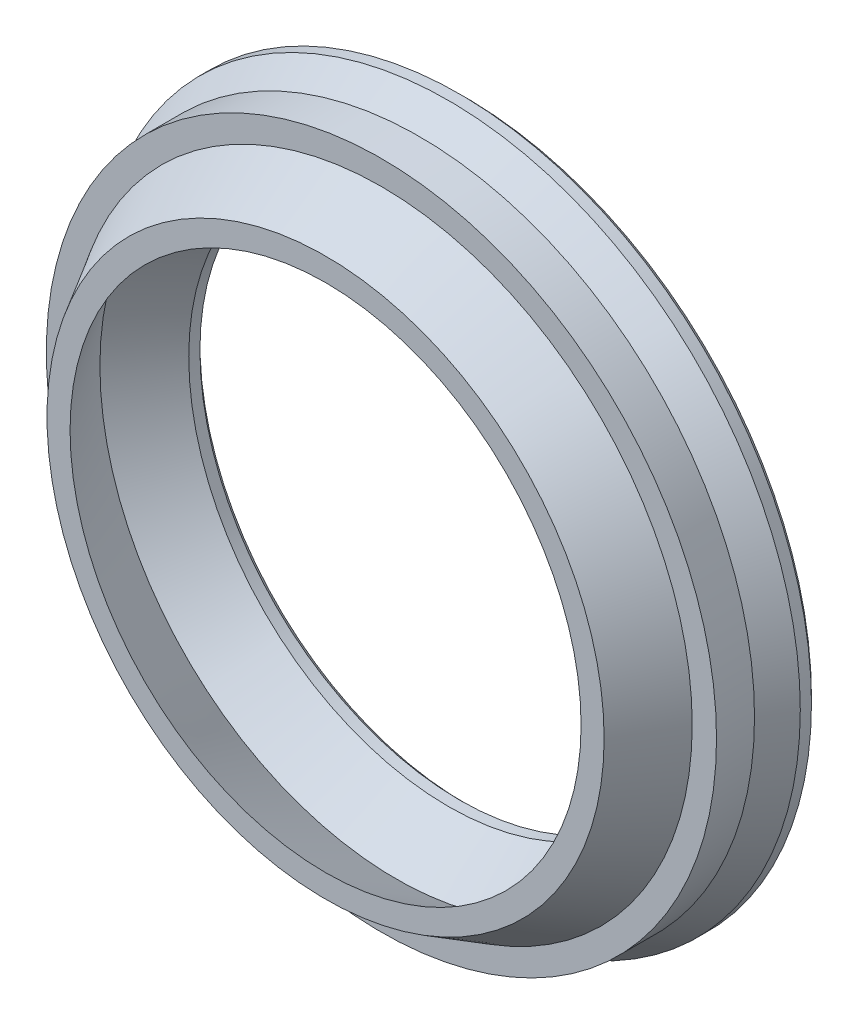
SolidWorks part; units mm, degrees
ref_plane "Front" through (0, 0, 0) normal (0, 0, 1) x (1, 0, 0)
ref_plane "Top" through (0, 0, 0) normal (0, 1, 0) x (1, 0, 0)
ref_plane "Right" through (0, 0, 0) normal (1, 0, 0) x (0, 0, -1)
sketch "Sketch1" plane through (21, 0, -3.1487) normal (0, 1, 0) x (-1, 0, 0)
  line L0 (21, 10.6441) -> (21, -7.4954) construction
  line L1 (41, -2.4526) -> (41, -0.1846)
  line L2 (41, -0.1846) -> (39.5495, -0.1846)
  line L3 (39.5495, -0.1846) -> (37.625, 3.1487)
  line L4 (37.625, 3.1487) -> (36.25, 3.1487)
  line L5 (41, -2.4526) -> (42, -4.1846)
  line L6 (42, -4.1846) -> (42, -5.1846)
  line L7 (42, -5.1846) -> (36.5, -5.1846)
  line L8 (36.5, -5.1846) -> (36.5, -4.1846)
  line L9 (36.5, -4.1846) -> (38.6835, -1.0662)
  line L10 (38.6835, -1.0662) -> (36.25, 3.1487)
  dimension "D1" = 30.5
  dimension "D2" = 31
  dimension "D5" = 1
  dimension "D6" = 3.3333
  dimension "D8" = 120
  dimension "D9" = 1.375
  dimension "D10" = 150
  dimension "D11" = 115
revolve "Body" add sketch "Sketch1" angle 360 about L0
sketch "Sketch2" plane through (19.25, 0, -11.3374) normal (0, 1, 0) x (-1, 0, 0)
  line L0 (19.25, 13.8484) -> (19.25, -2.511) construction
  line L2 (1, -0.9653) -> (1, -0.0415) construction
  line L3 (2, 3.0041) -> (0, 3.0041)
  line L5 (0, 3.0041) -> (0.4619, 3.8041)
  line L6 (0.4619, 3.8041) -> (1.5381, 3.8041)
  line L7 (1.5381, 3.8041) -> (2, 3.0041)
  line L9 (-1.75, 4.0041) -> (-1.75, 3.0041) construction
  line L10 (-1.75, 3.0041) -> (40.25, 3.0041) construction
  dimension "D1" = 2.75
  dimension "D2" = 0.8
  dimension "D3" = 60
  dimension "D4" = 2
revolve "Cut-Revolve1" cut sketch "Sketch2" angle 360 about L0
chamfer "EndChamfer" distance 0.3333 angle 45 2 edges at (15.5, 0, -8.3333) (21, 0, -8.3333)
equation "\"D5@Sketch1\" = \"h@Sketch1\" / 5"
equation "\"D9@Sketch1\" = \"S@Sketch1\" / 4"
equation "\"D6@Sketch1\" = 2 * \"h@Sketch1\" / 3"
equation "\"D1@EndChamfer\" = \"h@Sketch1\" / 15"
